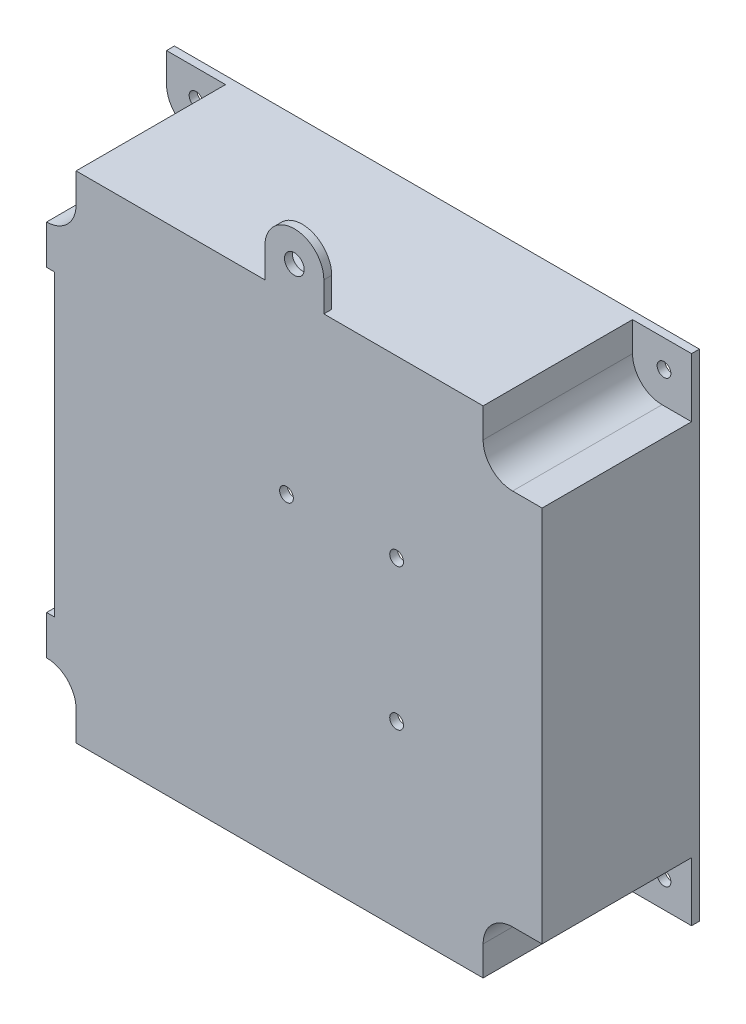
SolidWorks part; units mm, degrees
ref_plane "Plan de face" through (0, 0, 0) normal (0, 0, 1) x (1, 0, 0)
ref_plane "Plan de dessus" through (0, 0, 0) normal (0, 1, 0) x (1, 0, 0)
ref_plane "Plan de droite" through (0, 0, 0) normal (1, 0, 0) x (0, 0, -1)
sketch "Esquisse1" plane through (0, 0, 0) normal (0, 0, 1) x (1, 0, 0)
  line L1 (-151.4404, 157.0104) -> (-25.4404, 157.0104)
  line L2 (-151.4404, 157.0104) -> (-151.4404, 31.0104)
  line L3 (-151.4404, 31.0104) -> (-25.4404, 31.0104)
  line L4 (-25.4404, 157.0104) -> (-25.4404, 31.0104)
  dimension "D1" = 126
  dimension "D2" = 126
extrude "Boss.-Extru.1" add sketch "Esquisse1" along normal blind 40
sketch "Esquisse2" plane through (0, 0, 40) normal (0, 0, 1) x (1, 0, 0)
  line L0 (-40.4404, 31.0104) -> (-25.4404, 31.0104)
  line L1 (-25.4404, 31.0104) -> (-25.4404, 157.0104) construction
  line L2 (-40.4404, 38.5104) -> (-40.4404, 31.0104)
  line L4 (-151.4404, 31.0104) -> (-25.4404, 31.0104) construction
  line L5 (-32.9404, 46.0104) -> (-25.4404, 46.0104)
  line L6 (-25.4404, 46.0104) -> (-25.4404, 31.0104)
  arc A0 (-32.9404, 46.0104) -> (-40.4404, 38.5104) centre (-32.9404, 38.5104) ccw
  dimension "D1" = 7.5
  dimension "D3" = 15
  dimension "D2" = 7.5
extrude "Enlèv. mat.-Extru.1" cut sketch "Esquisse2" against normal blind 38
sketch "Esquisse4" plane through (0, 0, 2) normal (0, 0, 1) x (1, 0, 0)
  line L0 (-40.4404, 31.0104) -> (-25.4404, 31.0104) construction
  line L1 (-25.4404, 31.0104) -> (-25.4404, 46.0104) construction
  circle A0 centre (-32.4404, 38.0104) radius 1.75
  point P4 (-32.9404, 31.0104)
  dimension "D1" = 3.5
  dimension "D2" = 7
  dimension "D3" = 7
extrude "Enlèv. mat.-Extru.2" cut sketch "Esquisse4" against normal up to next
ref_plane "Plan1" through (0, 94.0104, 0) normal (0, -1, 0) x (-1, 0, 0)
mirror "Symétrie1" about plane through (0, 94.0104, 0) normal (0, -1, 0) of "Enlèv. mat.-Extru.2", "Enlèv. mat.-Extru.1"
ref_plane "Plan2" through (-88.4404, 0, 0) normal (-1, 0, 0) x (0, 0, 1)
sketch "Esquisse10" plane through (0, 0, 40) normal (0, 0, 1) x (1, 0, 0)
  line L0 (-151.4404, 31.0104) -> (-40.4404, 31.0104) construction
  line L2 (-151.4404, 46.0104) -> (-151.4404, 31.0104)
  line L3 (-151.4404, 31.0104) -> (-143.9404, 31.0104)
  line L4 (-143.9404, 31.0104) -> (-143.9404, 38.5104)
  arc A0 (-143.9404, 38.5104) -> (-151.4404, 46.0104) centre (-151.4404, 38.5104) ccw
  dimension "D1" = 15
  dimension "D2" = 7.5
extrude "Enlèv. mat.-Extru.5" cut sketch "Esquisse10" against normal blind 38
mirror "Symétrie3" about plane through (0, 94.0104, 0) normal (0, -1, 0) of "Enlèv. mat.-Extru.5"
shell "Coque1" thickness 2 removed face at (-30.6904, 150.0104, 0)
sketch "Esquisse12" plane through (0, 0, 2) normal (0, 0, 1) x (1, 0, 0)
  line L0 (-158.9404, 31.0104) -> (-158.9404, 38.5104)
  line L1 (-151.4404, 31.0104) -> (-158.9404, 31.0104)
  line L2 (-151.4404, 31.0104) -> (-151.4404, 46.0104)
  arc A0 (-151.4404, 46.0104) -> (-158.9404, 38.5104) centre (-151.4404, 38.5104) ccw
  dimension "D2" = 15
  dimension "D3" = 7.5
extrude "Boss.-Extru.3" add sketch "Esquisse12" against normal blind 2
sketch "Esquisse13" plane through (0, 0, 2) normal (0, 0, 1) x (1, 0, 0)
  line L1 (-158.9404, 31.0104) -> (-143.9404, 31.0104) construction
  circle A0 centre (-151.4404, 38.0104) radius 1.75
  dimension "D1" = 3.5
  dimension "D2" = 7
extrude "Enlèv. mat.-Extru.6" cut sketch "Esquisse13" against normal up to next
mirror "Symétrie5" about plane through (0, 94.0104, 0) normal (0, -1, 0) of "Boss.-Extru.3", "Enlèv. mat.-Extru.6"
sketch "Esquisse14" plane through (0, 0, 40) normal (0, 0, 1) x (1, 0, 0)
  line L0 (-40.4404, 157.0104) -> (-143.9404, 157.0104) construction
  line L1 (-25.4404, 46.0104) -> (-25.4404, 142.0104) construction
  circle A0 centre (-90.4404, 112.5104) radius 1.75
  dimension "D1" = 3.5
  dimension "D2" = 44.5
  dimension "D3" = 65
extrude "Enlèv. mat.-Extru.7" cut sketch "Esquisse14" against normal up to next
pattern_linear "Répétition linéaire1" count 2 spacing 28 along (1, 0, 0) of "Enlèv. mat.-Extru.7"
sketch "Esquisse15" plane through (0, 0, 40) normal (0, 0, 1) x (1, 0, 0)
  circle A0 centre (-62.4404, 76.5104) radius 1.75
  circle A1 centre (-62.4404, 112.5104) radius 1.75 construction
  circle A2 centre (-90.4404, 112.5104) radius 1.75 construction
  dimension "D1" = 3.5
  dimension "D2" = 36
  dimension "D3" = 28
extrude "Enlèv. mat.-Extru.8" cut sketch "Esquisse15" against normal up to next contours A0
sketch "Esquisse16" plane through (-151.4404, 0, 0) normal (-1, 0, 0) x (0, 0, 1)
  line L0 (0, 142.0104) -> (0, 46.0104) construction
  line L1 (0, 132.0104) -> (40, 132.0104)
  line L2 (0, 132.0104) -> (0, 56.0104)
  line L3 (0, 56.0104) -> (40, 56.0104)
  line L4 (40, 132.0104) -> (40, 56.0104)
  line L5 (40, 142.0104) -> (40, 46.0104) construction
  line L6 (2, 46.0104) -> (40, 46.0104) construction
  line L7 (2, 142.0104) -> (40, 142.0104) construction
  dimension "D1" = 10
  dimension "D2" = 10
extrude "Enlèv. mat.-Extru.9" cut sketch "Esquisse16" against normal up to surface (2 mm away) up to face at (-149.4404, 94.0104, 19)
sketch "Esquisse17" plane through (0, 0, 40) normal (0, 0, 1) x (1, 0, 0)
  line L0 (-40.4404, 157.0104) -> (-143.9404, 157.0104) construction
  line L1 (-95.9404, 157.0104) -> (-80.9404, 157.0104)
  line L2 (-95.9404, 157.0104) -> (-95.9404, 164.5104)
  line L3 (-88.4404, 22) -> (-88.4404, -22) construction
  line L4 (-80.9404, 157.0104) -> (-80.9404, 164.5104)
  arc A0 (-95.9404, 164.5104) -> (-80.9404, 164.5104) centre (-88.4404, 164.5104) cw
  dimension "D1" = 7.5
  dimension "D2" = 15
  dimension "D3" = 7.5
extrude "Boss.-Extru.4" add sketch "Esquisse17" against normal blind 2
sketch "Esquisse19" plane through (0, 0, 40) normal (0, 0, 1) x (1, 0, 0)
  line L0 (-80.9404, 157.0104) -> (-80.9404, 164.5104) construction
  circle A0 centre (-88.4404, 164.2604) radius 2.5
  arc A1 (-80.9404, 164.5104) -> (-95.9404, 164.5104) centre (-88.4404, 164.5104) ccw construction
  point P7 (-88.4404, 172.0104)
  dimension "D1" = 5
  dimension "D2" = 7.5
  dimension "D3" = 7.75
extrude "Enlèv. mat.-Extru.10" cut sketch "Esquisse19" against normal up to next
